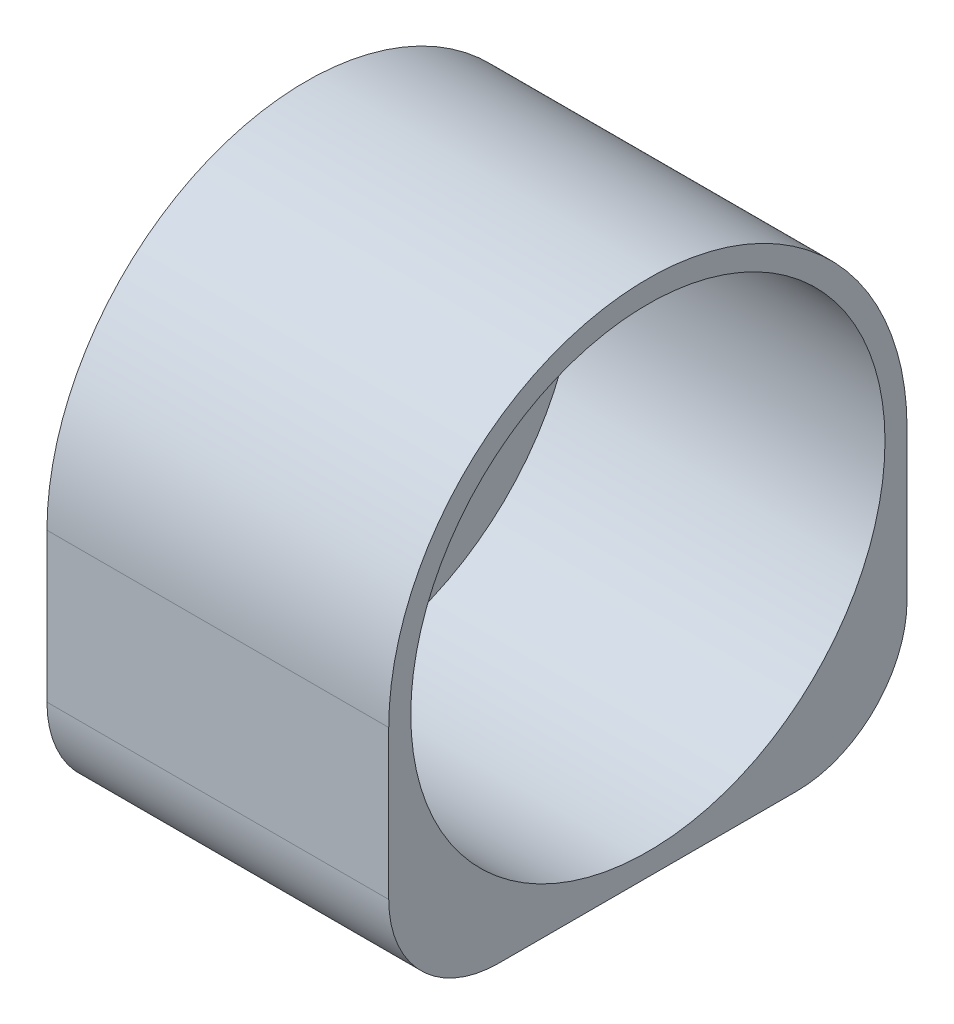
SolidWorks part; units mm, degrees
material "PLA"
ref_plane "Front Plane" through (0, 0, 0) normal (1, 0, 0) x (0, 1, 0)
ref_plane "Top Plane" through (0, 0, 0) normal (0, 0, 1) x (0, 1, 0)
ref_plane "Right Plane" through (0, 0, 0) normal (0, 1, 0) x (-1, 0, 0)
sketch "Sketch1" plane through (0, 0, 0) normal (1, 0, 0) x (0, 1, 0)
  line L4 (0, 6.5) -> (-20.5, 6.5)
  line L5 (0, 6.5) -> (0, -6.5)
  line L6 (0, -6.5) -> (-20.5, -6.5)
  line L7 (-20.5, 6.5) -> (-20.5, -6.5)
  line L8 (0, 0) -> (-24.2932, 0) construction
  line L10 (0, 6.5) -> (0, -6.5)
  line L11 (0, 18.7698) -> (0, -28.632) construction
  line L12 (-16.5, 6.5) -> (7.5, 6.5)
  line L13 (-16.5, 6.5) -> (-16.5, -6.5)
  line L14 (-16.5, -6.5) -> (7.5, -6.5)
  line L15 (7.5, 6.5) -> (7.5, -6.5)
  circle A2 centre (0, 0) radius 10.25
  circle A3 centre (0, 0) radius 21.5058
  circle A4 centre (0, 0) radius 23.5058
  dimension "D4" = 2
  dimension "D5" = 24
  dimension "D6" = 7.5
  dimension "D1" = 20.5
  dimension "D2" = 20.5
  dimension "D3" = 13
extrude "Boss-Extrude1" add sketch "Sketch1" along normal blind 28 contours A4 A3 region at (0, -22.841, 0)
extrude "Boss-Extrude4" add sketch "Sketch1<6>" against normal blind 3 contours L6 A3 L4 L12 A2 L14 | L13 L4 L7 L6 | L7 A3 | A4 A3 | L6 A2 L4 L12 L15 L14 region at (0, -18.5, 0) region at (0, -18.5, 7.1012) region at (0, -20.9031, 0) region at (0, 3.3593, 9.3934) region at (0, -22.841, 0)
sketch "Sketch1<6>" plane through (0, 0, 0) normal (1, 0, 0) x (0, 1, 0) same geometry as "Sketch1"
sketch "Sketch2" plane through (28, 0, 0) normal (1, 0, 0) x (0, 1, 0)
  line L0 (0, 23.5058) -> (-13.5058, 23.5058)
  line L1 (-23.5058, 13.5058) -> (-23.5058, -13.5058)
  line L2 (-13.5058, -23.5058) -> (0, -23.5058)
  line L3 (0, 0) -> (0, 26.9629) construction
  circle A0 centre (0, 0) radius 23.5058 construction
  arc A1 (-23.5058, -13.5058) -> (-13.5058, -23.5058) centre (-13.5058, -13.5058) ccw
  arc A2 (-13.5058, 23.5058) -> (-23.5058, 13.5058) centre (-13.5058, 13.5058) ccw
  circle A4 centre (0, 0) radius 23.5058
  arc A5 (0, 23.5058) -> (0, -23.5058) centre (0, 0) ccw
  circle M5 centre (0, 0) radius 23.5058
  dimension "D1" = 10
  dimension "D2" = 0
extrude "Boss-Extrude5" add sketch "Sketch2" against normal up to surface (31 mm away) contours L0 A2 L1 M5 | L1 A1 L2 M5 region at (28, -17.5887, 17.5887) region at (28, -17.5887, -17.5887) up to face at (-3, -4.5, 0)
sketch "Sketch3" plane through (0, -23.5058, 0) normal (0, -1, 0) x (1, 0, 0)
  circle A4 centre (12.3721, 0) radius 10.5
  dimension "D1" = 21
extrude "Cut-Extrude4" cut sketch "Sketch3" against normal blind 1 contours A4 region at (12.3721, -23.5058, 0)
